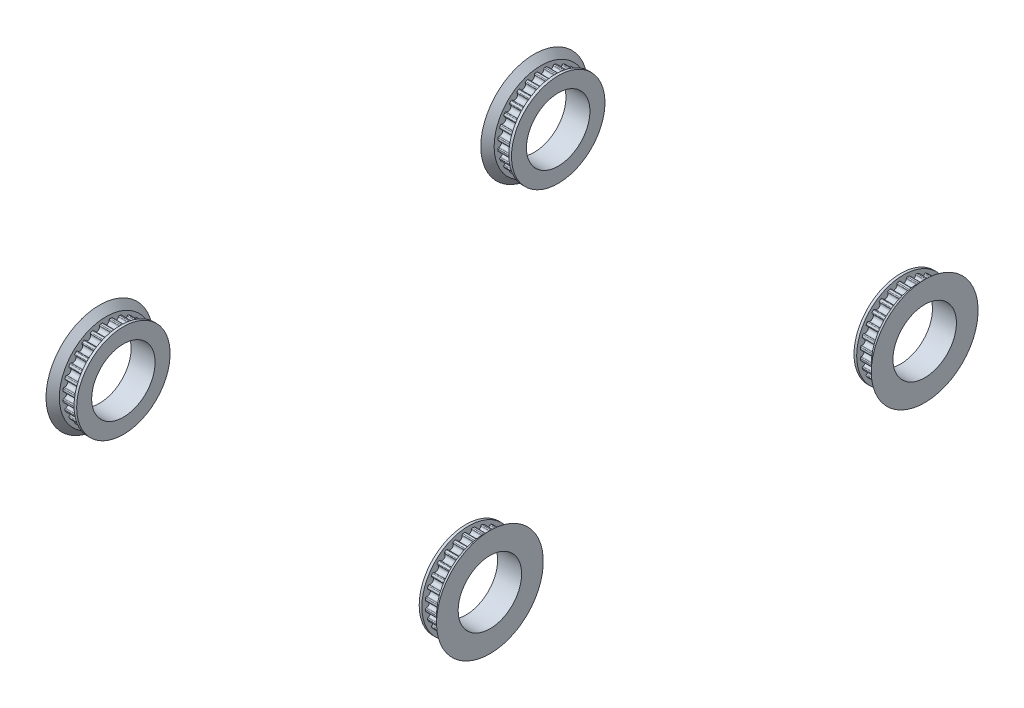
SolidWorks part; units mm, degrees
material "CF Nylon"
ref_plane "Front Plane" through (0, 0, 0) normal (0, 0, 1) x (1, 0, 0)
ref_plane "Top Plane" through (0, 0, 0) normal (0, 1, 0) x (1, 0, 0)
ref_plane "Right Plane" through (0, 0, 0) normal (1, 0, 0) x (0, 0, -1)
ref_plane "Plane1" through (54.4, 0, 0) normal (-1, 0, 0) x (0, 0, 1)
sketch "Sketch4" plane through (54.4, 0, 45.7) normal (1, 0, 0) x (0, 0, -1)
  line L0 (44.7968, 12.5781) -> (44.7799, 12.7158)
  line L2 (46.6201, 12.7158) -> (46.6032, 12.5781)
  line L3 (45.7, 12.689) -> (45.7, 12.989)
  line L4 (44.2457, 12.9073) -> (44.3812, 11.7049)
  line L6 (47.0188, 11.7049) -> (47.1543, 12.9073)
  circle A0 centre (45.7, 0) radius 11.779 construction
  circle A1 centre (45.7, 0) radius 13.37 construction
  circle A2 centre (45.7, 0) radius 12.989 construction
  arc A3 (44.7968, 12.5781) -> (46.6032, 12.5781) centre (45.7, 12.689) ccw
  arc A4 (46.6201, 12.7158) -> (46.8912, 12.9343) centre (46.8683, 12.6853) cw
  arc A5 (44.7799, 12.7158) -> (44.5088, 12.9343) centre (44.5317, 12.6853) ccw
  arc A6 (46.8912, 12.9343) -> (47.1543, 12.9073) centre (45.7, 0) cw
  arc A7 (44.5088, 12.9343) -> (44.2457, 12.9073) centre (45.7, 0) ccw
  arc A8 (44.3812, 11.7049) -> (47.0188, 11.7049) centre (45.7, 0) ccw
  circle A9 centre (45.7, 0) radius 9.525
  dimension "D4" = 0.91
  dimension "D6" = 0.25
  dimension "D7" = 26.74
  dimension "D8" = 19.05
  dimension "D3" = 1.21
  dimension "D2" = 0.381
  dimension "D5" = 14
  dimension "D1" = 12.857
extrude "Boss-Extrude2" add sketch "Sketch4" along normal mid plane 4.4 contours L4 A8 L6 A6 A4 L2 A3 L0 A5 A7 | A8 L4 A7 A5 L0 A3 L2 A4 A6 L6 A9
pattern_circular "CirPattern1" count 28 over 360 about axis through (0, 0, 0) along (1, 0, 0) of "Boss-Extrude2"
sketch "Sketch8" plane through (0, 0, 0) normal (0, 1, 0) x (1, 0, 0)
  line L0 (56.6, -9.525) -> (56.6, 9.525) construction
  line L1 (52.2, 14.025) -> (51.4, 14.025)
  line L2 (52.2, 14.025) -> (52.2, 9.525)
  line L3 (52.2, 9.525) -> (51.4, 9.525)
  line L4 (51.4, 14.025) -> (51.4, 9.525)
  line L6 (56.6, 14.025) -> (56.6, 9.525)
  line L7 (56.6, 9.525) -> (58.6, 9.525)
  line L8 (58.6, 16.025) -> (58.6, 9.525)
  line L9 (52.2, 9.525) -> (52.2, -9.525) construction
  line L10 (52.2, 9.525) -> (52.2, -9.525) construction
  line L11 (52.2, 0) -> (53.1141, 0) construction
  line L12 (58.6, 16.025) -> (56.6, 14.025)
  dimension "D1" = 0.8
  dimension "D2" = 4.5
  dimension "D3" = 2
  dimension "D4" = 45
revolve "Revolve1" add sketch "Sketch8" angle 360 about L11
sketch "Sketch5" plane through (0, 0, 0) normal (1, 0, 0) x (0, 0, -1)
  line L0 (0, 0) -> (-130.5, 0) construction
pattern_linear "LPattern1" count 2 spacing 130.5 along (0, 0, 1) of bodies 108 103
mirror "Mirror1" about plane through (0, 0, 0) normal (1, 0, 0) of bodies 104 108 103
equation "\"Teeth\"= 28"
equation "\"D1@Sketch4\"=360/\"Teeth\""
equation "\"Pitch Diameter\"= \"Teeth\" * .955"
equation "\"D1@CirPattern1\"=\"Teeth\""
equation "\"D7@Sketch4\"=\"Pitch Diameter\""
equation "\"D8@Sketch4\"=.75in"
